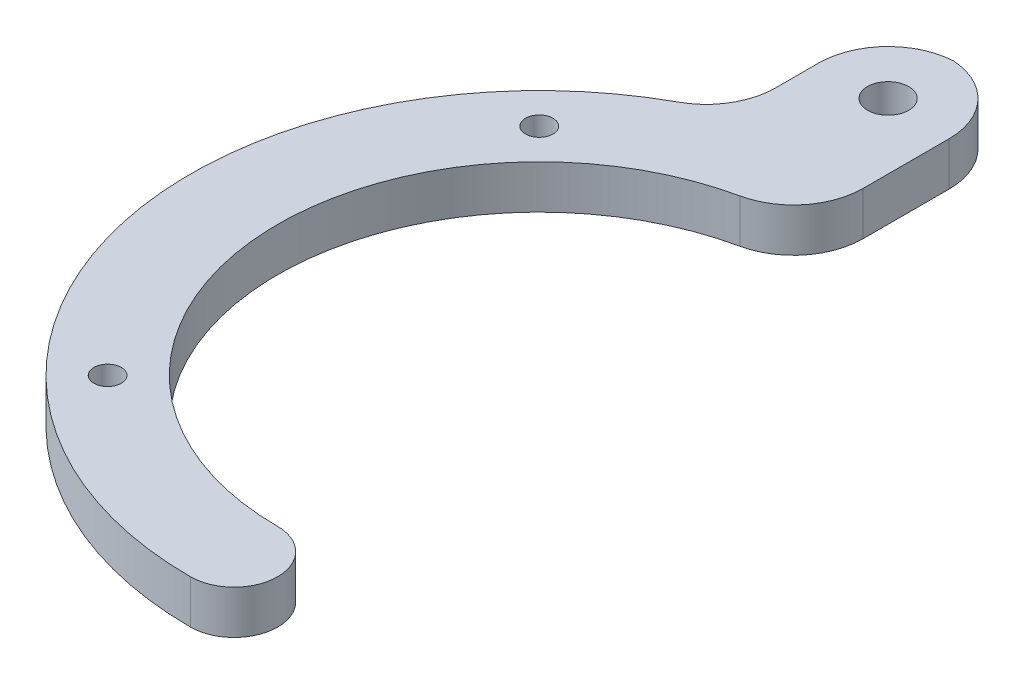
SolidWorks part; units mm, degrees
material "Pine"
ref_plane "Front Plane" through (0, 0, 0) normal (0, 0, 1) x (1, 0, 0)
ref_plane "Top Plane" through (0, 0, 0) normal (0, 1, 0) x (1, 0, 0)
ref_plane "Right Plane" through (0, 0, 0) normal (1, 0, 0) x (0, 0, -1)
sketch "Sketch1" plane through (0, 0, 0) normal (0, 1, 0) x (1, 0, 0)
  line L0 (0, 0) -> (19.05, 0)
  line L1 (19.05, 0) -> (19.05, -19.05)
  line L2 (0, 0) -> (0, -22.7571)
  line L3 (19.05, -19.05) -> (19.05, -120.65) construction
  line L4 (19.05, -31.75) -> (19.05, -19.05)
  line L5 (19.05, -9.525) -> (0, -9.525) construction
  line L6 (19.05, -69.85) -> (-12.3809, -38.4191) construction
  line L7 (19.05, -69.85) -> (-12.3809, -101.2809) construction
  arc A0 (19.05, -19.05) -> (19.05, -120.65) centre (19.05, -69.85) ccw
  arc A1 (19.05, -31.75) -> (19.05, -107.95) centre (19.05, -69.85) ccw
  arc A2 (19.05, -107.95) -> (19.05, -120.65) centre (19.05, -114.3) cw
  circle A3 centre (9.525, -9.525) radius 3
  circle A4 centre (19.05, -69.85) radius 44.45 construction
  circle A5 centre (-12.3809, -38.4191) radius 2
  circle A6 centre (-12.3809, -101.2809) radius 2
  dimension "D2" = 76.2
  dimension "D5" = 6
  dimension "D6" = 88.9
  dimension "D7" = 4
  dimension "D8" = 4
  dimension "D1" = 12.7
  dimension "D3" = 19.05
  dimension "D4" = 19.05
  dimension "D9" = 135
  dimension "D10" = 45
extrude "Boss-Extrude1" add sketch "Sketch1" along normal blind 6.35 contours L3 A1 L4 A0 | A0 L1 L0 L2 | A2 L3 region at (9.525, 0, 0.2968) region at (9.569, 0, 21.1296)
fillet "Fillet1" radius 10.16 4 edges at (0, 3.175, 22.7571) (19.05, 3.175, 31.75) (0, 3.175, 0) (19.05, 3.175, 0)
sketch "Sketch2" plane through (0, 6.35, 0) normal (0, 1, 0) x (1, 0, 0)
  line L0 (9.525, -4.525) -> (9.525, -3.255) construction
  line L1 (9.525, -3.255) -> (10.6293, -4.6485)
  line L2 (9.525, -3.255) -> (8.4207, -4.6485)
  line L3 (12.66, -4.095) -> (11.0069, -4.7496)
  line L4 (12.66, -4.095) -> (12.9196, -5.854)
  line L5 (12.025, -5.1949) -> (12.66, -4.095) construction
  line L6 (14.955, -6.39) -> (13.196, -6.1304)
  line L7 (14.955, -6.39) -> (14.3004, -8.0431)
  line L8 (13.8551, -7.025) -> (14.955, -6.39) construction
  line L9 (15.795, -9.525) -> (14.4015, -8.4207)
  line L10 (15.795, -9.525) -> (14.4015, -10.6293)
  line L11 (14.525, -9.525) -> (15.795, -9.525) construction
  line L12 (14.955, -12.66) -> (14.3004, -11.0069)
  line L13 (14.955, -12.66) -> (13.196, -12.9196)
  line L14 (13.8551, -12.025) -> (14.955, -12.66) construction
  line L15 (12.66, -14.955) -> (12.9196, -13.196)
  line L16 (12.66, -14.955) -> (11.0069, -14.3004)
  line L17 (12.025, -13.8551) -> (12.66, -14.955) construction
  line L18 (9.525, -15.795) -> (10.6293, -14.4015)
  line L19 (9.525, -15.795) -> (8.4207, -14.4015)
  line L20 (9.525, -14.525) -> (9.525, -15.795) construction
  line L21 (6.39, -14.955) -> (8.0431, -14.3004)
  line L22 (6.39, -14.955) -> (6.1304, -13.196)
  line L23 (7.025, -13.8551) -> (6.39, -14.955) construction
  line L24 (4.095, -12.66) -> (5.854, -12.9196)
  line L25 (4.095, -12.66) -> (4.7496, -11.0069)
  line L26 (5.1949, -12.025) -> (4.095, -12.66) construction
  line L27 (3.255, -9.525) -> (4.6485, -10.6293)
  line L28 (3.255, -9.525) -> (4.6485, -8.4207)
  line L29 (4.525, -9.525) -> (3.255, -9.525) construction
  line L31 (4.095, -6.39) -> (4.7496, -8.0431)
  line L33 (4.095, -6.39) -> (5.854, -6.1304)
  line L35 (5.1949, -7.025) -> (4.095, -6.39) construction
  line L37 (6.39, -4.095) -> (6.1304, -5.854)
  line L39 (6.39, -4.095) -> (8.0431, -4.7496)
  line L41 (7.025, -5.1949) -> (6.39, -4.095) construction
  arc A0 (6.1304, -5.854) -> (5.854, -6.1304) centre (9.525, -9.525) ccw construction
  arc A1 (6.1304, -5.854) -> (5.854, -6.1304) centre (9.525, -9.525) ccw
  arc A2 (4.7496, -8.0431) -> (4.6485, -8.4207) centre (9.525, -9.525) ccw construction
  arc A3 (4.7496, -8.0431) -> (4.6485, -8.4207) centre (9.525, -9.525) ccw
  arc A4 (4.6485, -10.6293) -> (4.7496, -11.0069) centre (9.525, -9.525) ccw construction
  arc A5 (4.6485, -10.6293) -> (4.7496, -11.0069) centre (9.525, -9.525) ccw
  arc A6 (5.854, -12.9196) -> (6.1304, -13.196) centre (9.525, -9.525) ccw construction
  arc A7 (5.854, -12.9196) -> (6.1304, -13.196) centre (9.525, -9.525) ccw
  arc A8 (8.0431, -14.3004) -> (8.4207, -14.4015) centre (9.525, -9.525) ccw construction
  arc A9 (8.0431, -14.3004) -> (8.4207, -14.4015) centre (9.525, -9.525) ccw
  arc A10 (10.6293, -14.4015) -> (11.0069, -14.3004) centre (9.525, -9.525) ccw construction
  arc A11 (10.6293, -14.4015) -> (11.0069, -14.3004) centre (9.525, -9.525) ccw
  arc A12 (12.9196, -13.196) -> (13.196, -12.9196) centre (9.525, -9.525) ccw construction
  arc A13 (12.9196, -13.196) -> (13.196, -12.9196) centre (9.525, -9.525) ccw
  arc A14 (14.3004, -11.0069) -> (14.4015, -10.6293) centre (9.525, -9.525) ccw construction
  arc A15 (14.3004, -11.0069) -> (14.4015, -10.6293) centre (9.525, -9.525) ccw
  arc A16 (14.4015, -8.4207) -> (14.3004, -8.0431) centre (9.525, -9.525) ccw construction
  arc A17 (14.4015, -8.4207) -> (14.3004, -8.0431) centre (9.525, -9.525) ccw
  arc A18 (13.196, -6.1304) -> (12.9196, -5.854) centre (9.525, -9.525) ccw construction
  arc A19 (13.196, -6.1304) -> (12.9196, -5.854) centre (9.525, -9.525) ccw
  arc A20 (11.0069, -4.7496) -> (10.6293, -4.6485) centre (9.525, -9.525) ccw construction
  arc A21 (11.0069, -4.7496) -> (10.6293, -4.6485) centre (9.525, -9.525) ccw
  arc A22 (8.4207, -4.6485) -> (8.0431, -4.7496) centre (9.525, -9.525) ccw construction
  arc A23 (8.4207, -4.6485) -> (8.0431, -4.7496) centre (9.525, -9.525) ccw
  point P52 (9.525, -9.525)
  dimension "D1" = 10
  dimension "D3" = 1.778
  dimension "D2" = 1.27
extrude "Cut-Extrude1" [suppressed] cut sketch "Sketch2" against normal through all
equation "\"D6@Sketch1\" = \"D2@Sketch1\" + \"D1@Sketch1\""
